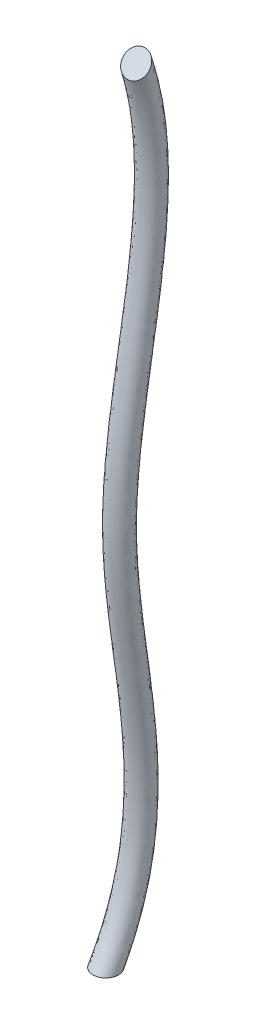
SolidWorks part; units mm, degrees
ref_plane "Front Plane" through (0, 0, 0) normal (0, 0, 1) x (1, 0, 0)
ref_plane "Top Plane" through (0, 0, 0) normal (0, 1, 0) x (1, 0, 0)
ref_plane "Right Plane" through (0, 0, 0) normal (1, 0, 0) x (0, 0, -1)
sketch "Sketch1" plane through (0, 0, 0) normal (0, 1, 0) x (1, 0, 0)
  circle A0 centre (0, 0) radius 0.32
sketch "Sketch2" plane through (0, 0, 0) normal (1, 0, 0) x (0, 0, -1)
  spline S0 degree 3 poles (0, 0) (1.7381, 3.0944) (-1.086, 9.4266) (1.8105, 15.8412) (0.757, 19.1138) knots 0 0 0 0 0.486697 1 1 1 1
sweep "Sweep1" add profiles "Sketch1" path "Sketch2"
